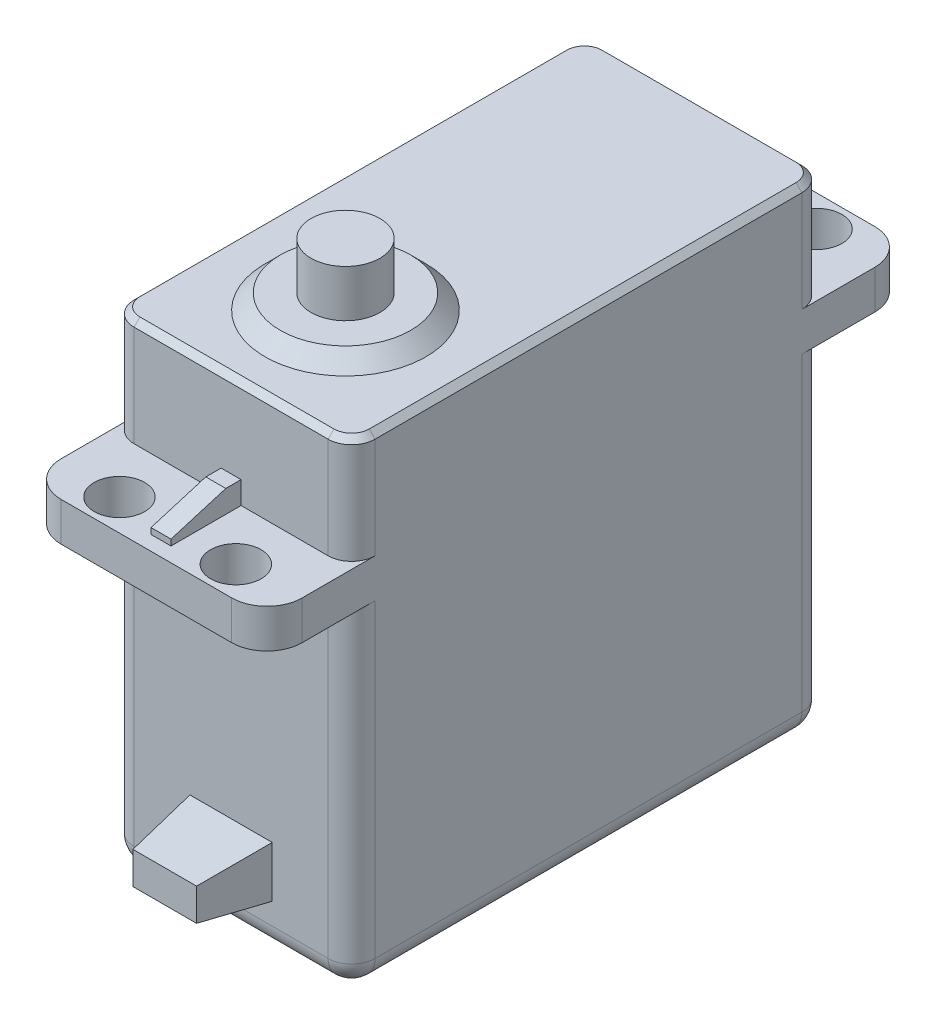
SolidWorks part; units mm, degrees
ref_plane "Front Plane" through (0, 0, 0) normal (0, 0, 1) x (1, 0, 0)
ref_plane "Top Plane" through (0, 0, 0) normal (0, 1, 0) x (1, 0, 0)
ref_plane "Right Plane" through (0, 0, 0) normal (1, 0, 0) x (0, 0, -1)
sketch "Sketch1" plane through (0, 0, 0) normal (1, 0, 0) x (0, 0, -1)
  line L1 (0, 0) -> (40.3, 0)
  line L2 (0, 0) -> (0, 40.75)
  line L3 (0, 40.75) -> (40.3, 40.75)
  line L4 (40.3, 0) -> (40.3, 40.75)
  dimension "D1" = 40.75
  dimension "D2" = 40.3
extrude "Boss-Extrude1" add sketch "Sketch1" along normal mid plane 20.5
sketch "Sketch2" plane through (0, 40.75, 0) normal (0, 1, 0) x (1, 0, 0)
  line L0 (10.25, 0) -> (-10.25, 0) construction
  line L1 (0, -25.3275) -> (0, 25.3275) construction
  circle A0 centre (0, 9.73) radius 2.93
  dimension "D2" = 5.86
  dimension "D1" = 9.73
extrude "Boss-Extrude2" add sketch "Sketch2" along normal blind 5.3
sketch "Sketch3" plane through (0, 40.75, 0) normal (0, 1, 0) x (1, 0, 0)
  circle A1 centre (0, 9.73) radius 2.93 construction
  circle A3 centre (0, 9.73) radius 6.85
  dimension "D1" = 13.7
extrude "Boss-Extrude3" add sketch "Sketch3" along normal blind 1.3
chamfer "Chamfer1" distance 1.3 angle 45 1 edges at (0, 42.05, -2.88)
sketch "Sketch4" plane through (0, 0, 0) normal (0, 1, 0) x (1, 0, 0)
  line L1 (-10.25, 0) -> (10.25, 0)
  line L2 (-10.25, 0) -> (-10.25, -7.2)
  line L3 (-10.25, -7.2) -> (10.25, -7.2)
  line L4 (10.25, 0) -> (10.25, -7.2)
  line L5 (10.25, 40.3) -> (-10.25, 40.3)
  line L6 (10.25, 40.3) -> (10.25, 47.5)
  line L7 (10.25, 47.5) -> (-10.25, 47.5)
  line L8 (-10.25, 40.3) -> (-10.25, 47.5)
  dimension "D1" = 7.2
extrude "Boss-Extrude4" add sketch "Sketch4" along normal blind 3.3 from offset 28.36
ref_plane "Plane1" through (0, 0, -20.15) normal (0, 0, 1) x (1, 0, 0)
sketch "Sketch5" plane through (0, 31.66, 0) normal (0, 1, 0) x (1, 0, 0)
  line L0 (0, -25.3275) -> (0, 25.3275) construction
  line L1 (4.95, -4.545) -> (4.95, 44.845) construction
  line L3 (-11.275, 20.15) -> (11.275, 20.15) construction
  circle A0 centre (4.95, -4.545) radius 2.15
  circle A1 centre (-4.95, -4.545) radius 2.15
  circle A2 centre (4.95, 44.845) radius 2.15
  circle A3 centre (-4.95, 44.845) radius 2.15
  point P8 (4.95, 20.15)
  dimension "D1" = 4.3
  dimension "D2" = 9.9
  dimension "D3" = 49.39
extrude "Cut-Extrude1" cut sketch "Sketch5" against normal up to next
fillet "Fillet1" radius 2 12 edges at (0, 0, 0) (10.25, 0, -20.15) (0, 0, -40.3) (-10.25, 0, -20.15) (-10.25, 36.205, 0) (10.25, 36.205, 0) (-10.25, 36.205, -40.3) (10.25, 36.205, -40.3) (-10.25, 14.18, -40.3) (10.25, 14.18, -40.3) (-10.25, 14.18, 0) (10.25, 14.18, 0)
fillet "Fillet2" radius 3 4 edges at (-10.25, 30.01, -47.5) (10.25, 30.01, -47.5) (10.25, 30.01, 7.2) (-10.25, 30.01, 7.2)
sketch "Sketch7" plane through (0, 0, 0) normal (1, 0, 0) x (0, 0, -1)
  line L0 (0, 31.66) -> (0, 33.57)
  line L1 (0, 31.66) -> (0, 40.75) construction
  line L2 (0, 33.57) -> (-1.3, 33.57)
  line L3 (-1.3, 33.57) -> (-5.96, 32.1696)
  line L4 (-5.96, 32.1696) -> (-5.96, 31.66)
  line L5 (-4.2, 31.66) -> (-7.2, 31.66) construction
  line L6 (-5.96, 31.66) -> (0, 31.66)
  line L7 (-4.2, 28.36) -> (2, 28.36) construction
  dimension "D1" = 1.3
  dimension "D2" = 0.5096
  dimension "D3" = 5.96
  dimension "D4" = 5.21
extrude "Boss-Extrude5" add sketch "Sketch7" along normal mid plane 1.7
mirror "Mirror1" about plane through (0, 0, -20.15) normal (0, 0, 1) of "Boss-Extrude5"
chamfer "Chamfer2" distance 0.5 angle 45 8 edges at (-10.25, 40.75, -20.15) (-9.6642, 40.75, -39.7142) (-9.6642, 40.75, -0.5858) (0, 40.75, -40.3) (0, 40.75, 0) (9.6642, 40.75, -39.7142) (9.6642, 40.75, -0.5858) (10.25, 40.75, -20.15)
sketch "Sketch8" plane through (0, 0, 0) normal (0, 0, 1) x (1, 0, 0)
  line L0 (8.25, 0) -> (-8.25, 0) construction
  line L1 (-3.5, 8.17) -> (3.5, 8.17)
  line L2 (-3.5, 8.17) -> (-3.5, 3.84)
  line L3 (-3.5, 3.84) -> (3.5, 3.84)
  line L4 (3.5, 8.17) -> (3.5, 3.84)
  point P4 (0, 3.84)
  dimension "D1" = 7
  dimension "D2" = 4.33
  dimension "D3" = 3.84
extrude "Boss-Extrude6" add sketch "Sketch8" along normal blind 5.64 draft 8
move or copy body "Body-Move/Copy1" [suppressed] bodies to move or copy 108
equation "\"D1@Sketch2\"=6.8+5.86/2"
equation "\"D2@Sketch5\"=5.6+4.3"
equation "\"D3@Sketch5\"=45.09+\"D1@Sketch5\""
